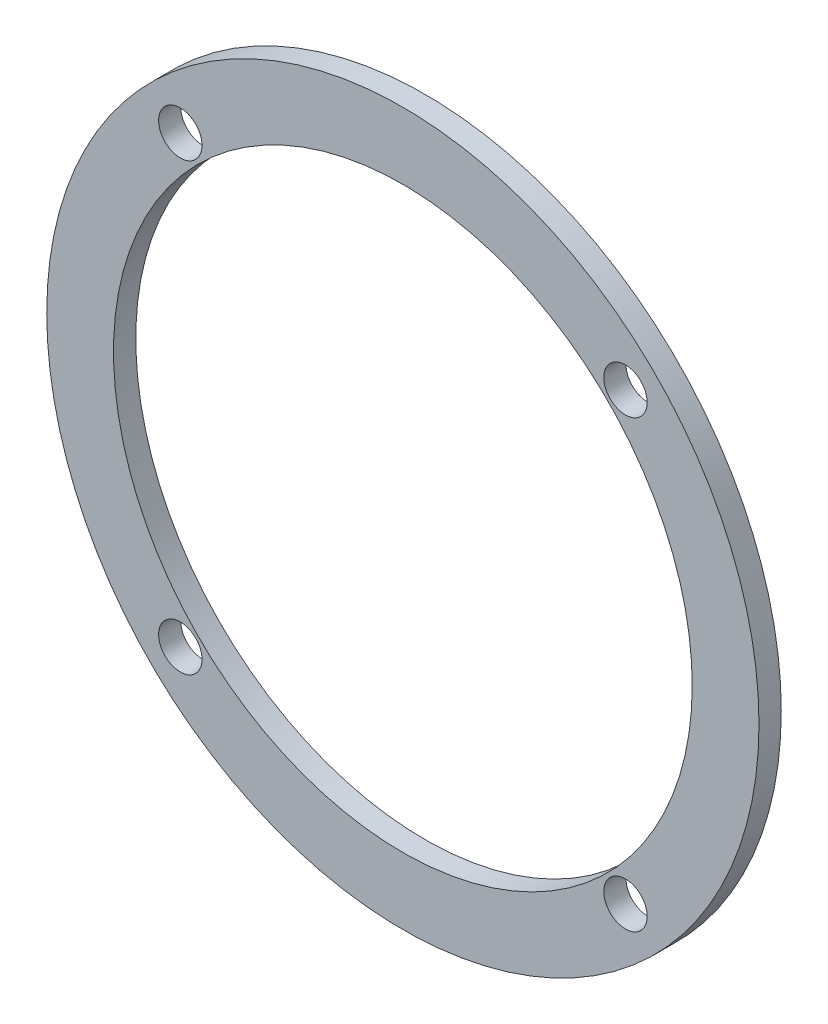
SolidWorks part; units mm, degrees
ref_plane "Front Plane" through (0, 0, 0) normal (0, 0, 1) x (1, 0, 0)
ref_plane "Top Plane" through (0, 0, 0) normal (0, 1, 0) x (1, 0, 0)
ref_plane "Right Plane" through (0, 0, 0) normal (1, 0, 0) x (0, 0, -1)
sketch "Sketch1" plane through (0, 0, 0) normal (0, 0, 1) x (1, 0, 0)
  line L0 (0, 20) -> (0, 0) construction
  line L1 (20, -20) -> (-20, -20) construction
  line L2 (20, -20) -> (20, 20) construction
  line L3 (20, 20) -> (-20, 20) construction
  line L4 (-20, -20) -> (-20, 20) construction
  line L5 (20, -20) -> (-20, 20) construction
  line L6 (20, 20) -> (-20, -20) construction
  line L7 (0, 0) -> (20, 0) construction
  circle A0 centre (0, 0) radius 25 construction
  circle A1 centre (-20, 20) radius 1.95
  circle A2 centre (20, 20) radius 1.95
  circle A3 centre (20, -20) radius 1.95
  circle A4 centre (-20, -20) radius 1.95
  circle A5 centre (0, 0) radius 26
  circle A6 centre (0, 0) radius 32
  dimension "Screw Holes Speaker" = 3.9
  dimension "Backlash" = 1
  dimension "speakerDiam" = 50
  dimension "speakerCenterDist" = 40
  dimension "boxInteriorDiam" = 64
extrude "Boss-Extrude1" add sketch "Sketch1" along normal blind 2 contours A6 A4 A3 A1 A2 A5 region at (-31.0949, 0, 0)
equation "\"speakerCenterDist\" = 40"
equation "\"speakerDiam\" = 50"
equation "\"boxInteriorDiam\" = 64"
